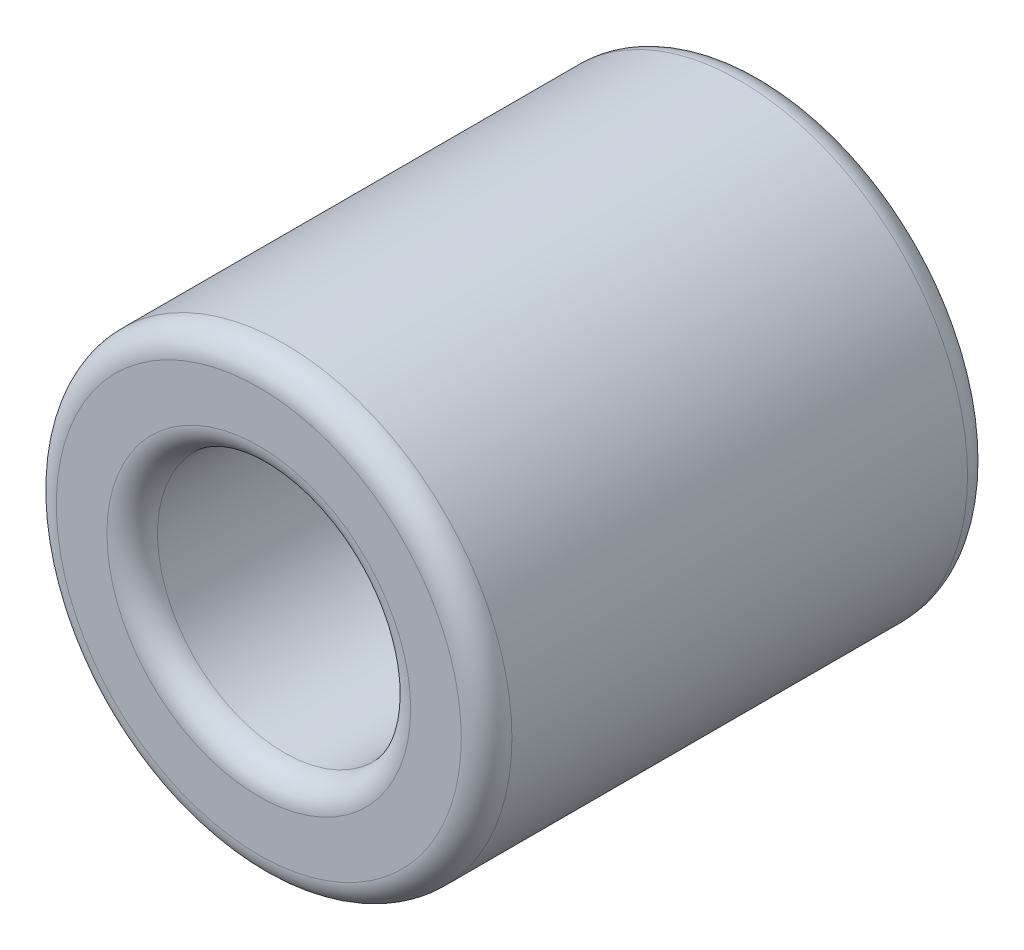
SolidWorks part; units mm, degrees
ref_plane "Front" through (0, 0, 0) normal (0, 0, 1) x (1, 0, 0)
ref_plane "Top" through (0, 0, 0) normal (0, 1, 0) x (1, 0, 0)
ref_plane "Right" through (0, 0, 0) normal (1, 0, 0) x (0, 0, -1)
sketch "Szkic1" plane through (0, 0, 0) normal (0, 0, 1) x (1, 0, 0)
  circle A0 centre (0, 0) radius 5
  circle A1 centre (0, 0) radius 9
  dimension "D1" = 18
  dimension "D2" = 10
extrude "Dodanie-wyciągnięcie1" add sketch "Szkic1" along normal blind 20
fillet "Zaokrąglenie1" radius 1 4 edges at (5, 0, 0) (9, 0, 0) (5, 0, 20) (9, 0, 20)
